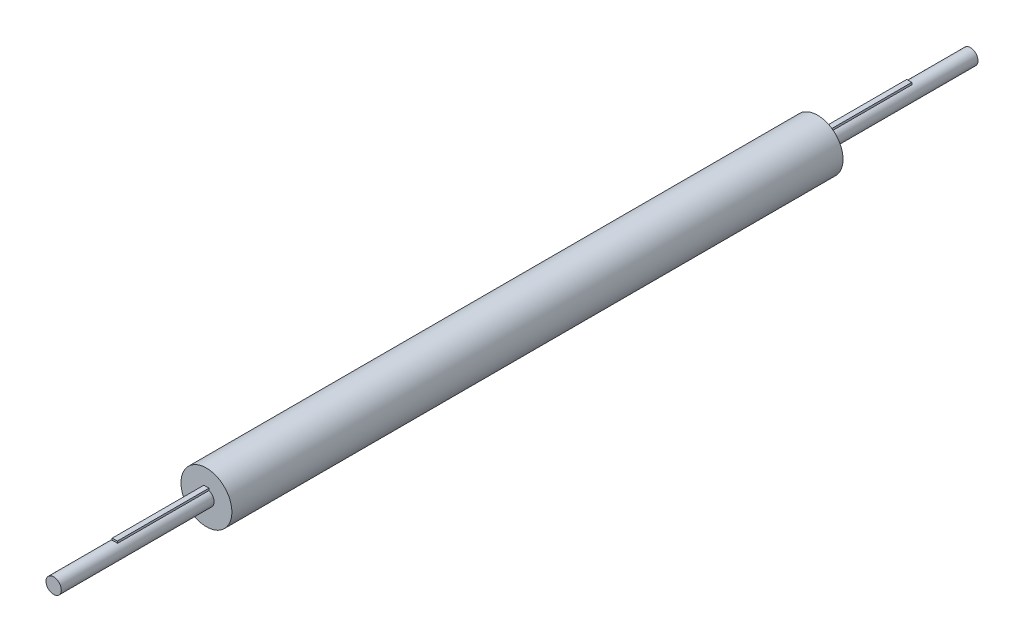
SolidWorks part; units mm, degrees
material "AISI 1010 Steel, hot rolled bar"
ref_plane "Front Plane" through (0, 0, 0) normal (0, 0, 1) x (1, 0, 0)
ref_plane "Top Plane" through (0, 0, 0) normal (0, 1, 0) x (1, 0, 0)
ref_plane "Right Plane" through (0, 0, 0) normal (1, 0, 0) x (0, 0, -1)
sketch "Sketch1" plane through (0, 0, 0) normal (0, 0, 1) x (1, 0, 0)
  circle A0 centre (0, 0) radius 50
  dimension "D1" = 100
sketch "Sketch4" plane through (0, 0, 0) normal (0, 0, 1) x (1, 0, 0)
  line L1 (-5, 14.1421) -> (-5, 18.3)
  line L4 (5, 18.3) -> (5, 14.1421)
  line L5 (-5, 18.3) -> (5, 18.3)
  arc A2 (-5, 14.1421) -> (5, 14.1421) centre (0, 0) ccw
  dimension "D2" = 10
  dimension "D1" = 15
  dimension "D3" = 18.3
  dimension "D4" = 5
sketch "Sketch5" [suppressed] plane through (0, 0, 0) normal (0, 0, 1) x (1, 0, 0)
  line L0 (7, 7.1414) -> (7, -7.1414) construction
  line L1 (-7, 7.1414) -> (-7, -7.1414) construction
  line L2 (7, 7.1414) -> (7, -7.1414)
  line L3 (-7, 7.1414) -> (-7, -7.1414)
  line L7 (-5, 18.3) -> (-5, 14.1421)
  line L8 (-5, 18.3) -> (-5, 14.1421)
  line L9 (5, 18.3) -> (-5, 18.3)
  line L10 (5, 18.3) -> (-5, 18.3)
  line L11 (5, 14.1421) -> (5, 18.3)
  line L12 (5, 14.1421) -> (5, 18.3)
  arc A1 (-5, 14.1421) -> (5, 14.1421) centre (0, 0) ccw
  arc A3 (-5, 14.1421) -> (5, 14.1421) centre (0, 0) ccw
  dimension "D1" = 0
extrude "Boss-Extrude4" add sketch "Sketch4" along normal mid plane 1600
sketch "Sketch6" plane through (0, 0, 0) normal (0, 0, 1) x (1, 0, 0)
  circle A0 centre (0, 0) radius 50
  dimension "D1" = 100
extrude "Boss-Extrude5" add sketch "Sketch6" along normal mid plane 1200
ref_axis "Axis1" through (0, 0, 600) along (0, 0, -1)
sketch "Sketch7" plane through (0, 0, 0) normal (0, 0, 1) x (1, 0, 0)
  circle A0 centre (0, 0) radius 15
  dimension "D1" = 30
extrude "Boss-Extrude6" add sketch "Sketch7" along normal blind 100 from offset 800
mirror "Mirror1" about plane through (0, 0, 0) normal (0, 0, 1) of "Boss-Extrude6"
ref_axis "Axis2" through (0, 0, 600) along (0, 0, -1)
sketch "Sketch8" plane through (0, 0, 800) normal (0, 0, 1) x (1, 0, 0)
  line L3 (5, 14.1421) -> (5, 18.3)
  line L4 (5, 18.3) -> (-5, 18.3)
  line L5 (-5, 18.3) -> (-5, 14.1421)
  line L6 (5, 14.1421) -> (5, 18.3)
  line L7 (5, 18.3) -> (-5, 18.3)
  line L8 (-5, 18.3) -> (-5, 14.1421)
  arc A1 (5, 14.1421) -> (-5, 14.1421) centre (0, 0) ccw
  arc A2 (5, 14.1421) -> (-5, 14.1421) centre (0, 0) ccw
  dimension "D1" = 0
extrude "Cut-Extrude1" cut sketch "Sketch8" against normal blind 20
sketch "Sketch9" plane through (0, 0, -800) normal (0, 0, -1) x (-1, 0, 0)
  line L3 (-5, 18.3) -> (-5, 14.1421)
  line L4 (5, 14.1421) -> (5, 18.3)
  line L5 (5, 18.3) -> (-5, 18.3)
  line L6 (-5, 18.3) -> (-5, 14.1421)
  line L7 (5, 14.1421) -> (5, 18.3)
  line L8 (5, 18.3) -> (-5, 18.3)
  arc A1 (5, 14.1421) -> (-5, 14.1421) centre (0, 0) ccw
  arc A2 (5, 14.1421) -> (-5, 14.1421) centre (0, 0) ccw
  dimension "D1" = 0
extrude "Cut-Extrude2" cut sketch "Sketch9" against normal blind 20
